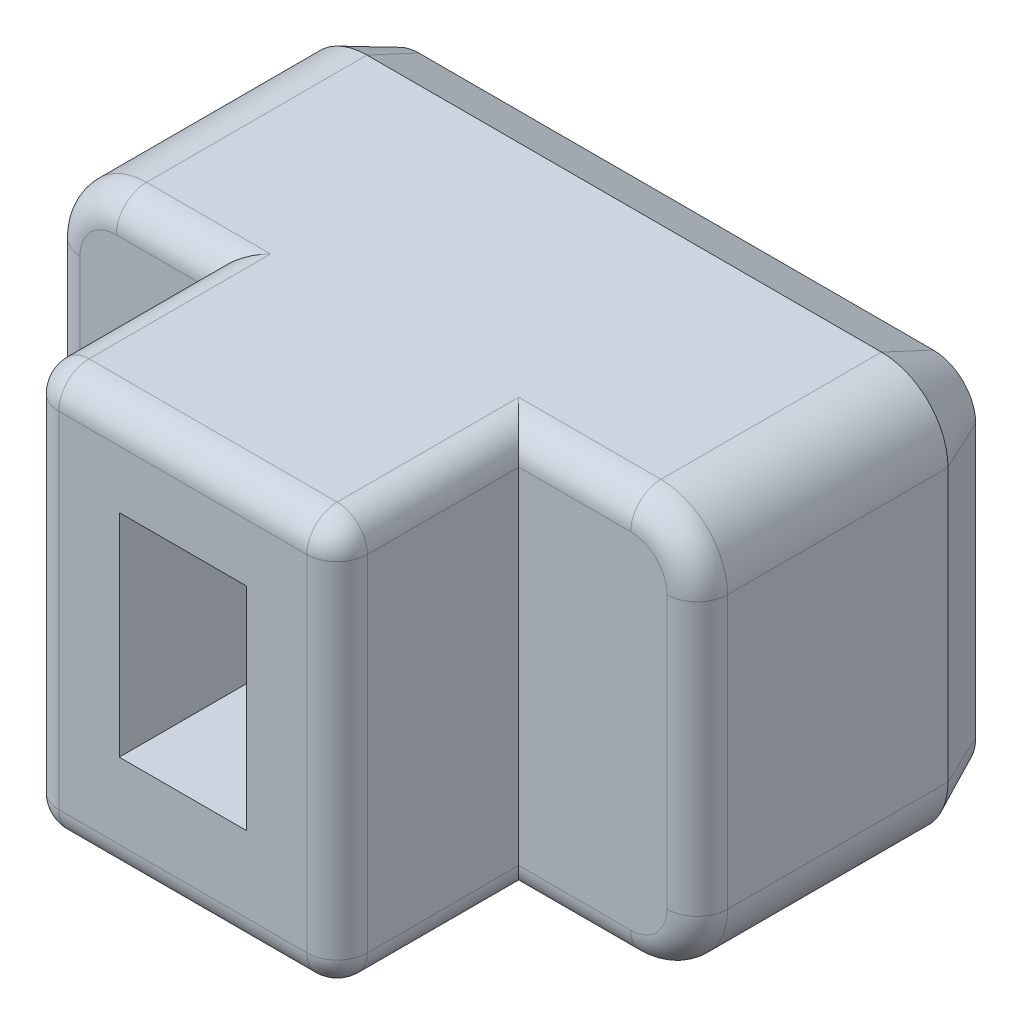
SolidWorks part; units mm, degrees
ref_plane "Plan de face" through (0, 0, 0) normal (0, 0, 1) x (1, 0, 0)
ref_plane "Plan de dessus" through (0, 0, 0) normal (0, 1, 0) x (1, 0, 0)
ref_plane "Plan de droite" through (0, 0, 0) normal (1, 0, 0) x (0, 0, -1)
sketch "Esquisse2" plane through (0, 0, 0) normal (0, 0, 1) x (1, 0, 0)
  line L1 (1.1, 0) -> (9.6, 0)
  line L2 (0, 1.1) -> (0, 5.6)
  line L3 (1.1, 6.7) -> (9.6, 6.7)
  line L4 (10.7, 1.1) -> (10.7, 5.6)
  arc A0 (9.6, 6.7) -> (10.7, 5.6) centre (9.6, 5.6) cw
  arc A1 (9.6, 0) -> (10.7, 1.1) centre (9.6, 1.1) ccw
  arc A2 (1.1, 0) -> (0, 1.1) centre (1.1, 1.1) cw
  arc A3 (0, 5.6) -> (1.1, 6.7) centre (1.1, 5.6) cw
  point P7 (10.7, 6.7)
  point P12 (0, 0)
  point P15 (0, 6.7)
  dimension "D3" = 1.1
  dimension "D1" = 10.7
  dimension "D2" = 6.7
extrude "Boss.-Extru.1" add sketch "Esquisse2" along normal blind 8
sketch "Esquisse3" plane through (0, 0, 8) normal (0, 0, 1) x (1, 0, 0)
  line L0 (0, 5.6) -> (0, 1.1) construction
  line L1 (4.15, 5.25) -> (6.25, 5.25)
  line L2 (4.15, 5.25) -> (4.15, 1.75)
  line L3 (4.15, 1.75) -> (6.25, 1.75)
  line L4 (6.25, 5.25) -> (6.25, 1.75)
  line L5 (10.7, 1.1) -> (10.7, 5.6) construction
  line L6 (9.6, 6.7) -> (1.1, 6.7) construction
  line L7 (1.1, 0) -> (9.6, 0) construction
  dimension "D1" = 2.1
  dimension "D2" = 3.5
  dimension "D3" = 4.15
  dimension "D4" = 4.45
  dimension "D5" = 1.45
  dimension "D6" = 1.75
extrude "Enlèv. mat.-Extru.1" cut sketch "Esquisse3" against normal blind 3
sketch "Esquisse4" plane through (0, 0, 8) normal (0, 0, 1) x (1, 0, 0)
  line L0 (2.65, 6.7) -> (2.65, 0)
  line L1 (9.6, 6.7) -> (1.1, 6.7) construction
  line L2 (1.1, 0) -> (9.6, 0) construction
  line L3 (2.65, 0) -> (7.75, 0)
  line L4 (7.75, 0) -> (7.75, 6.7)
  line L5 (7.75, 6.7) -> (2.65, 6.7)
  line L6 (4.15, 5.25) -> (4.15, 1.75) construction
  line L7 (6.25, 1.75) -> (6.25, 5.25) construction
  dimension "D1" = 1.5
  dimension "D2" = 1.5
extrude "Enlèv. mat.-Extru.2" cut sketch "Esquisse4" against normal blind 3 flip side to cut
fillet "Congé1" radius 0.5 18 edges at (8.675, 0, 5) (10.3778, 0.3222, 5) (10.7, 3.35, 5) (10.3778, 6.3778, 5) (1.875, 6.7, 5) (0.3222, 6.3778, 5) (1.875, 0, 5) (0.3222, 0.3222, 5) (7.75, 6.7, 6.5) (2.65, 6.7, 6.5) (7.75, 0, 6.5) (2.65, 0, 6.5) (2.65, 3.35, 8) (5.2, 6.7, 8) (7.75, 3.35, 8) (5.2, 0, 8) (8.675, 6.7, 5) (0, 3.35, 5)
chamfer "Chanfrein1" distance 0.4 angle 65 8 edges at (5.35, 0, 0) (10.3778, 0.3222, 0) (0.3222, 0.3222, 0) (10.7, 3.35, 0) (0, 3.35, 0) (10.3778, 6.3778, 0) (0.3222, 6.3778, 0) (5.35, 6.7, 0) first distance on face at (5.35, 3.35, 0)
ref_plane "Plan1" through (0, 0, 0.2) normal (0, 0, 1) x (1, 0, 0)
sketch "Esquisse5" plane through (0, 0, 0.2) normal (0, 0, 1) x (1, 0, 0)
  line L0 (-0.9378, 5.3566) -> (11.6517, 5.3566) construction
  text T0 "ARM" font "Century Gothic" height 4
extrude "Enlèv. mat.-Extru.3" cut sketch "Esquisse5" against normal blind 0.3
extrude "Boss.-Extru.2" add sketch "Esquisse5<3>" against normal blind 0.2 from offset 0.2 offset against normal yes
sketch "Esquisse5<3>" plane through (0, 0, 0.2) normal (0, 0, 1) x (1, 0, 0) same geometry as "Esquisse5"
